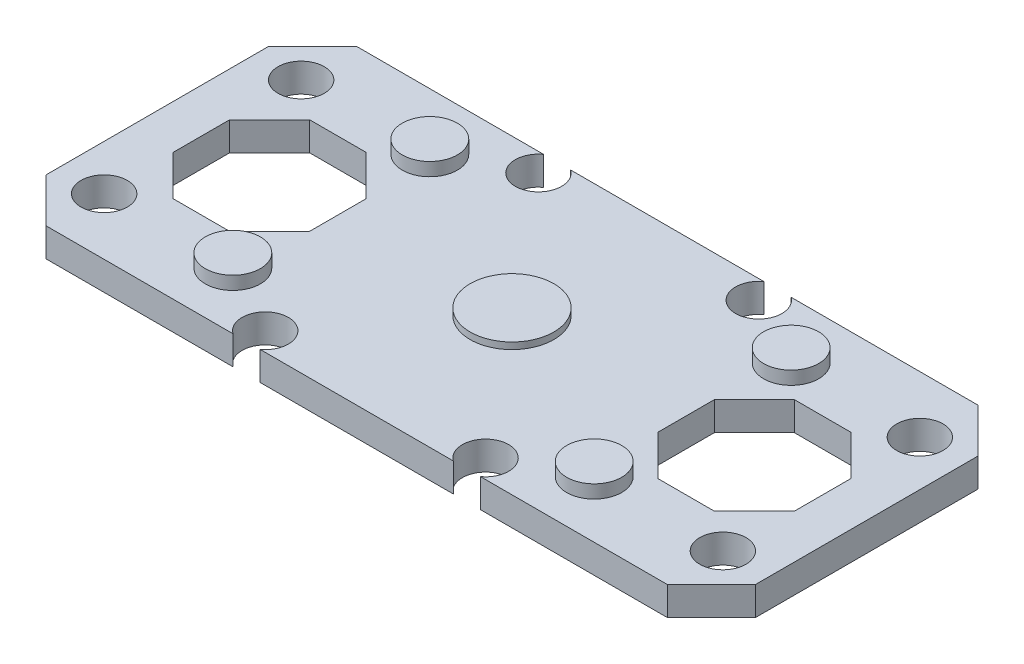
SolidWorks part; units mm, degrees
ref_plane "Front" through (0, 0, 0) normal (0, 0, 1) x (1, 0, 0)
ref_plane "Top" through (0, 0, 0) normal (0, 1, 0) x (1, 0, 0)
ref_plane "Right" through (0, 0, 0) normal (1, 0, 0) x (0, 0, -1)
sketch "Sketch1" plane through (0, 0, 0) normal (0, 1, 0) x (1, 0, 0)
  line L0 (-5.5671, 8.9535) -> (5.5671, 8.9535)
  line L1 (-6.35, -7.874) -> (6.35, -7.874) construction
  line L2 (-6.35, -7.874) -> (-6.35, 7.874) construction
  line L3 (-6.35, 7.874) -> (6.35, 7.874) construction
  line L4 (6.35, -7.874) -> (6.35, 7.874) construction
  line L5 (-6.35, -7.874) -> (6.35, 7.874) construction
  line L6 (-6.35, 7.874) -> (6.35, -7.874) construction
  line L7 (-17.8308, -5.6769) -> (17.8308, -5.6769) construction
  line L8 (-17.8308, -5.6769) -> (-17.8308, 5.6769) construction
  line L9 (-17.8308, 5.6769) -> (17.8308, 5.6769) construction
  line L10 (17.8308, -5.6769) -> (17.8308, 5.6769) construction
  line L11 (-17.8308, -5.6769) -> (17.8308, 5.6769) construction
  line L12 (-17.8308, 5.6769) -> (17.8308, -5.6769) construction
  line L13 (-10.414, -5.6769) -> (10.414, -5.6769) construction
  line L14 (-10.414, -5.6769) -> (-10.414, 5.6769) construction
  line L15 (-10.414, 5.6769) -> (10.414, 5.6769) construction
  line L16 (10.414, -5.6769) -> (10.414, 5.6769) construction
  line L17 (-10.414, -5.6769) -> (10.414, 5.6769) construction
  line L18 (-10.414, 5.6769) -> (10.414, -5.6769) construction
  line L19 (-20.447, -8.9535) -> (-7.1329, -8.9535)
  line L20 (-20.447, -8.9535) -> (-20.447, 8.9535)
  line L21 (-20.447, 8.9535) -> (-7.1329, 8.9535)
  line L22 (20.447, -8.9535) -> (20.447, 8.9535)
  line L23 (-20.447, -8.9535) -> (20.447, 8.9535) construction
  line L24 (-20.447, 8.9535) -> (20.447, -8.9535) construction
  line L25 (7.1329, 8.9535) -> (20.447, 8.9535)
  line L26 (7.1329, -8.9535) -> (20.447, -8.9535)
  line L27 (-5.5671, -8.9535) -> (5.5671, -8.9535)
  circle A0 centre (-17.8308, 5.6769) radius 1.3335
  arc A1 (-7.1329, 8.9535) -> (-5.5671, 8.9535) centre (-6.35, 7.874) ccw
  arc A2 (5.5671, 8.9535) -> (7.1329, 8.9535) centre (6.35, 7.874) ccw
  circle A3 centre (17.8308, 5.6769) radius 1.3335
  circle A4 centre (17.8308, -5.6769) radius 1.3335
  arc A5 (7.1329, -8.9535) -> (5.5671, -8.9535) centre (6.35, -7.874) ccw
  arc A6 (-5.5671, -8.9535) -> (-7.1329, -8.9535) centre (-6.35, -7.874) ccw
  circle A7 centre (-17.8308, -5.6769) radius 1.3335
  circle A8 centre (-10.414, 5.6769) radius 1.5875
  circle A9 centre (10.414, 5.6769) radius 1.5875
  circle A10 centre (10.414, -5.6769) radius 1.5875
  circle A11 centre (-10.414, -5.6769) radius 1.5875
  point P0 (0, 0)
  point P6 (0, 0)
  point P11 (0, 0)
  point P16 (0, 0)
  dimension "D8" = 2.667
  dimension "D9" = 3.175
  dimension "D1" = 12.7
  dimension "D2" = 15.748
  dimension "D3" = 11.3538
  dimension "D4" = 35.6616
  dimension "D5" = 40.894
  dimension "D6" = 17.907
  dimension "D7" = 20.828
extrude "Boss-Extrude1" add sketch "Sketch1" along normal blind 1.651
chamfer "Chamfer1" distance 2.54 angle 45 4 edges at (-20.447, 0.8255, 8.9535) (-20.447, 0.8255, -8.9535) (20.447, 0.8255, -8.9535) (20.447, 0.8255, 8.9535)
extrude "Boss-Extrude2" add sketch "Sketch1<2>" along normal blind 2.413 contours A8 | A9 | A10 | A11
sketch "Sketch1<2>" plane through (0, 0, 0) normal (0, 1, 0) x (1, 0, 0) same geometry as "Sketch1"
extrude "Cut-Extrude1" cut sketch "Sketch1<3>" along normal blind 0.889 contours A11 | A10 | A9 | A8
sketch "Sketch1<3>" plane through (0, 0, 0) normal (0, 1, 0) x (1, 0, 0) same geometry as "Sketch1"
sketch "Sketch3" plane through (0, 1.651, 0) normal (0, 1, 0) x (1, 0, 0)
  line L1 (-17.907, -3.937) -> (17.907, -3.937) construction
  line L2 (-17.907, -3.937) -> (-17.907, 3.937) construction
  line L3 (-17.907, 3.937) -> (17.907, 3.937) construction
  line L4 (17.907, -3.937) -> (17.907, 3.937) construction
  line L5 (-17.907, -3.937) -> (17.907, 3.937) construction
  line L6 (-17.907, 3.937) -> (17.907, -3.937) construction
  line L7 (-10.033, 1.6308) -> (-12.3392, 3.937)
  line L8 (-12.3392, 3.937) -> (-15.6008, 3.937)
  line L9 (-15.6008, 3.937) -> (-17.907, 1.6308)
  line L10 (-17.907, 1.6308) -> (-17.907, -1.6308)
  line L11 (-17.907, -1.6308) -> (-15.6008, -3.937)
  line L12 (-15.6008, -3.937) -> (-12.3392, -3.937)
  line L13 (-12.3392, -3.937) -> (-10.033, -1.6308)
  line L14 (-10.033, -1.6308) -> (-10.033, 1.6308)
  line L15 (17.907, 1.6308) -> (15.6008, 3.937)
  line L16 (15.6008, 3.937) -> (12.3392, 3.937)
  line L17 (12.3392, 3.937) -> (10.033, 1.6308)
  line L18 (10.033, 1.6308) -> (10.033, -1.6308)
  line L19 (10.033, -1.6308) -> (12.3392, -3.937)
  line L20 (12.3392, -3.937) -> (15.6008, -3.937)
  line L21 (15.6008, -3.937) -> (17.907, -1.6308)
  line L22 (17.907, -1.6308) -> (17.907, 1.6308)
  circle A0 centre (-13.97, 0) radius 3.937 construction
  circle A1 centre (13.97, 0) radius 3.937 construction
  point P0 (0, 0)
  dimension "D1" = 7.874
  dimension "D2" = 35.814
extrude "Cut-Extrude3" cut sketch "Sketch3" against normal through all
sketch "Sketch4" plane through (0, 1.651, 0) normal (0, 1, 0) x (1, 0, 0)
  circle A0 centre (0, 0) radius 2.413
  dimension "D1" = 4.826
extrude "Boss-Extrude3" add sketch "Sketch4" along normal blind 0.381
extrude "Cut-Extrude4" cut sketch "Sketch4<2>" along normal blind 0.635 from surface starting at face at (-13.97, 0, 0)
sketch "Sketch4<2>" plane through (0, 1.651, 0) normal (0, 1, 0) x (1, 0, 0) same geometry as "Sketch4"
